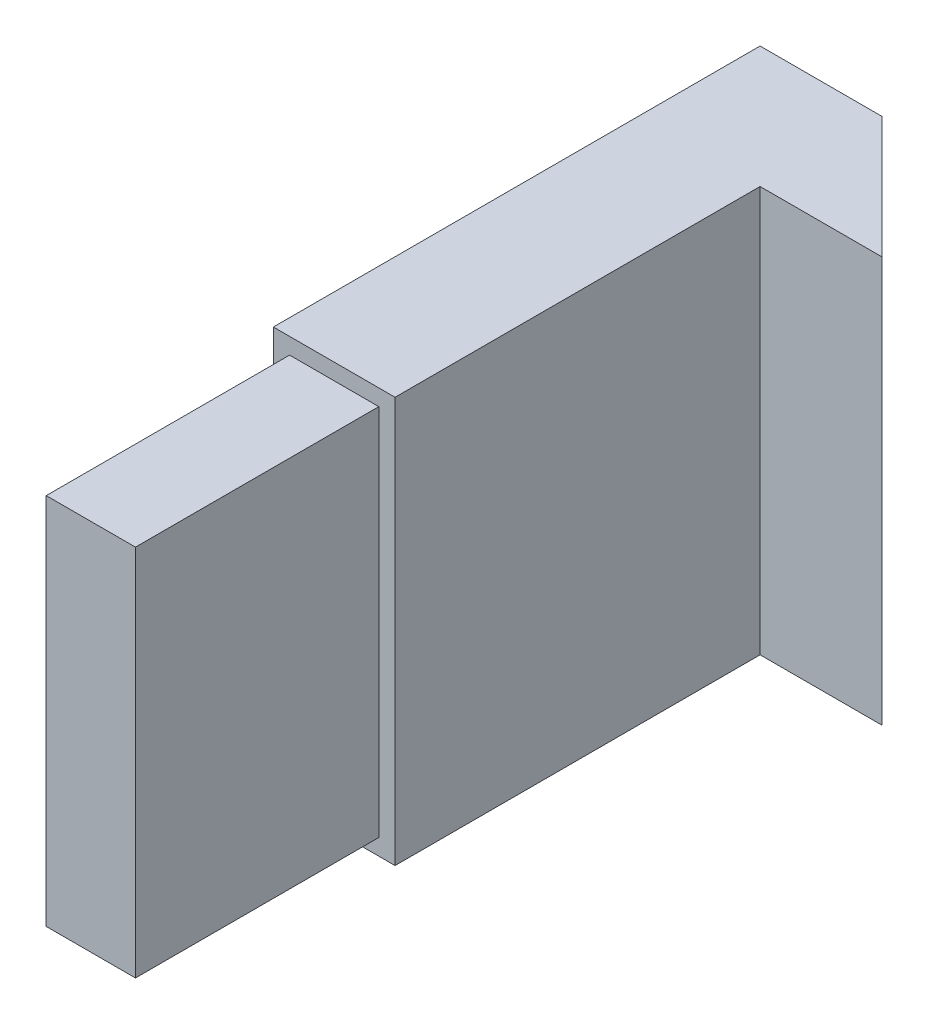
SolidWorks part; units mm, degrees
ref_plane "Front Plane" through (0, 0, 0) normal (0, 0, 1) x (1, 0, 0)
ref_plane "Top Plane" through (0, 0, 0) normal (0, 1, 0) x (1, 0, 0)
ref_plane "Right Plane" through (0, 0, 0) normal (1, 0, 0) x (0, 0, -1)
sketch "Sketch1" plane through (0, 0, 0) normal (0, 1, 0) x (1, 0, 0)
  line L0 (2.25, 1.5) -> (0.75, 3)
  line L1 (-0.75, -3) -> (0.75, -3)
  line L5 (-0.7, -3) -> (0.7, -3)
  line L7 (-0.75, 3) -> (0.75, 3)
  line L8 (-0.75, 3) -> (-0.75, -3)
  line L9 (-0.75, -3) -> (0.75, -3)
  line L10 (0.75, 1.5) -> (0.75, -3)
  line L11 (-0.75, 3) -> (0.75, -3) construction
  line L12 (-0.75, -3) -> (0.75, 3) construction
  line L13 (0.75, 1.5) -> (0.75, 3) construction
  line L15 (0.75, 1.5) -> (2.25, 1.5)
  point P6 (0, 0)
  dimension "D1" = 1.5
  dimension "D3" = 6
extrude "Boss-Extrude1" add sketch "Sketch1" along normal blind 5 contours L1 | L10 L15 L0 L7 L8 L1 region at (0.1389, 0, -0.2222)
sketch "Sketch2" plane through (0, 0, 3) normal (0, 0, 1) x (1, 0, 0)
  line L0 (-0.55, 2.5) -> (0.55, 2.5) construction
  line L1 (0, 4.8) -> (0, 0.2) construction
  line L8 (-0.55, 0.2) -> (0.55, 0.2)
  line L9 (0.55, 0.2) -> (0.55, 4.8)
  line L10 (0.55, 4.8) -> (-0.55, 4.8)
  line L11 (-0.55, 4.8) -> (-0.55, 0.2)
  line L12 (-0.55, 0.2) -> (0.55, 0.2)
  line L13 (0.55, 0.2) -> (0.55, 4.8)
  line L14 (0.55, 4.8) -> (-0.55, 4.8)
  line L15 (-0.55, 4.8) -> (-0.55, 0.2)
  dimension "D1" = 0.2
extrude "Boss-Extrude2" add sketch "Sketch2" along normal blind 3
ref_point "Point1"
ref_axis "Axis1" through (0, 2.5, -6.2512) along (0, 0, 1)
